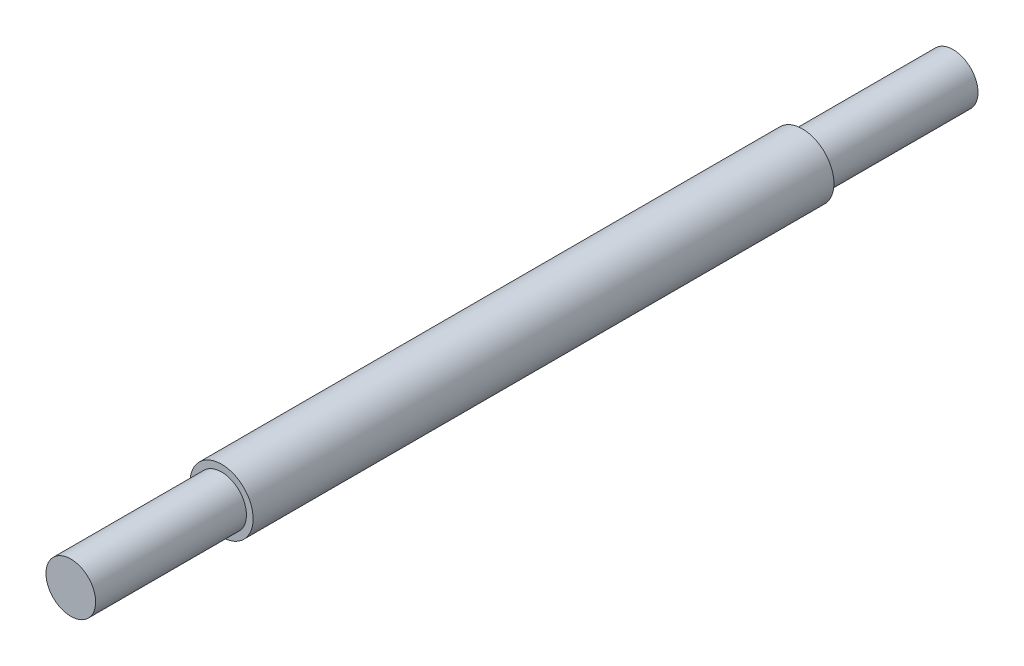
SolidWorks part; units mm, degrees
ref_plane "Front Plane" through (0, 0, 0) normal (0, 0, 1) x (1, 0, 0)
ref_plane "Top Plane" through (0, 0, 0) normal (0, 1, 0) x (1, 0, 0)
ref_plane "Right Plane" through (0, 0, 0) normal (1, 0, 0) x (0, 0, -1)
sketch "Sketch2" plane through (0, 0, 0) normal (0, 0, 1) x (1, 0, 0)
  circle A0 centre (0, 0) radius 2.5
  dimension "D1" = 5
extrude "Boss-Extrude1" add sketch "Sketch2" along normal blind 44.3738 and the other way blind 44.3738
sketch "Sketch3" plane through (0, 0, 0) normal (0, 0, 1) x (1, 0, 0)
  circle A0 centre (0, 0) radius 3.175
  dimension "D1" = 6.35
extrude "Boss-Extrude2" add sketch "Sketch3" along normal blind 29.21 and the other way blind 29.21
